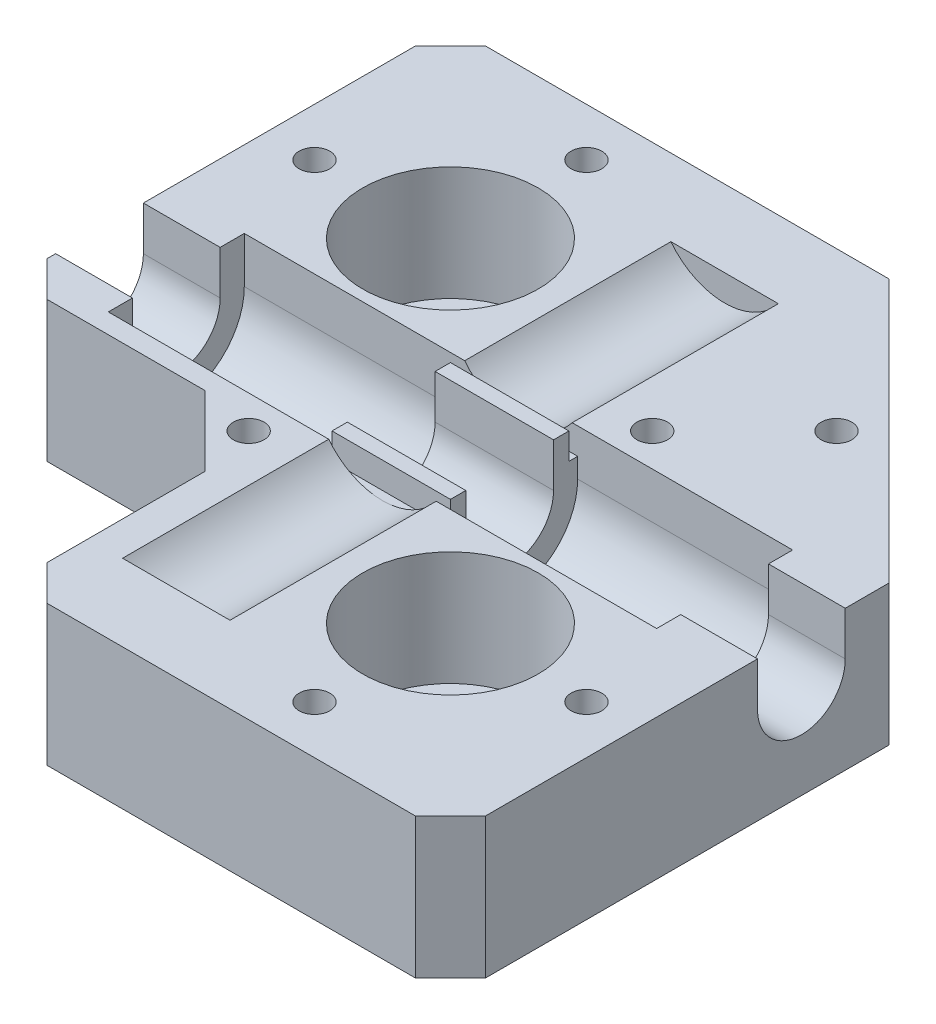
SolidWorks part; units mm, degrees
ref_plane "Front Plane" through (0, 0, 0) normal (0, 0, 1) x (1, 0, 0)
ref_plane "Top Plane" through (0, 0, 0) normal (0, 1, 0) x (1, 0, 0)
ref_plane "Right Plane" through (0, 0, 0) normal (1, 0, 0) x (0, 0, -1)
sketch "Sketch1" plane through (0, 0, 0) normal (0, 1, 0) x (1, 0, 0)
  line L1 (-40, -40) -> (40, -40)
  line L2 (-40, -40) -> (-40, 40)
  line L3 (-40, 40) -> (40, 40)
  line L4 (40, -40) -> (40, 40)
  line L5 (-40, -40) -> (40, 40) construction
  line L6 (-40, 40) -> (40, -40) construction
  point P0 (0, 0)
  dimension "D1" = 80
  dimension "D2" = 80
extrude "Boss-Extrude1" add sketch "Sketch1" against normal blind 16
sketch "Sketch2" plane through (0, 0, 0) normal (0, 1, 0) x (1, 0, 0)
  circle A0 centre (-11.5, -11.5) radius 1.75
  circle A1 centre (11.5, 11.5) radius 1.75
  circle A2 centre (22, 22) radius 1.75
  circle A3 centre (19, -34.5) radius 1.75
  circle A4 centre (34.5, -19) radius 1.75
  circle A5 centre (-34.5, 19) radius 1.75
  circle A6 centre (-19, 34.5) radius 1.75
  dimension "D1" = 3.5
  dimension "D2" = 3.5
  dimension "D3" = 3.5
  dimension "D4" = 3.5
  dimension "D5" = 3.5
  dimension "D6" = 3.5
  dimension "D7" = 3.5
  dimension "D8" = 11.5
  dimension "D9" = 11.5
  dimension "D10" = 11.5
  dimension "D11" = 11.5
  dimension "D12" = 22
  dimension "D13" = 22
  dimension "D14" = 34.5
  dimension "D15" = 34.5
  dimension "D16" = 19
  dimension "D17" = 19
  dimension "D18" = 34.5
  dimension "D19" = 19
  dimension "D20" = 19
  dimension "D21" = 34.5
extrude "Cut-Extrude1" cut sketch "Sketch2" against normal through all both and the other way through all
sketch "Sketch3" plane through (0, 0, 0) normal (0, 1, 0) x (1, 0, 0)
  line L1 (31.25, -7.75) -> (6.75, -7.75)
  line L2 (31.25, -7.75) -> (31.25, 7.75)
  line L3 (31.25, 7.75) -> (6.75, 7.75)
  line L4 (6.75, -7.75) -> (6.75, 7.75)
  line L5 (31.25, -7.75) -> (6.75, 7.75) construction
  line L6 (31.25, 7.75) -> (6.75, -7.75) construction
  line L7 (-6.75, -7.75) -> (-31.25, -7.75)
  line L8 (-6.75, -7.75) -> (-6.75, 7.75)
  line L9 (-6.75, 7.75) -> (-31.25, 7.75)
  line L10 (-31.25, -7.75) -> (-31.25, 7.75)
  line L11 (-6.75, -7.75) -> (-31.25, 7.75) construction
  line L12 (-6.75, 7.75) -> (-31.25, -7.75) construction
  point P0 (19, 0)
  point P5 (-19, 0)
  dimension "D1" = 15.5
  dimension "D2" = 0
  dimension "D3" = 24.5
  dimension "D4" = 19
  dimension "D5" = 24.5
  dimension "D6" = 15.5
  dimension "D7" = 0
  dimension "D8" = 19
extrude "Cut-Extrude2" cut sketch "Sketch3" against normal blind 13
fillet "Fillet1" radius 7.75 4 edges at (19, -13, 7.75) (19, -13, -7.75) (-19, -13, 7.75) (-19, -13, -7.75)
sketch "Sketch4" plane through (0, 0, 0) normal (0, 1, 0) x (1, 0, 0)
  line L1 (-7.75, -31.25) -> (7.75, -31.25)
  line L2 (-7.75, -31.25) -> (-7.75, -6.75)
  line L3 (-7.75, -6.75) -> (7.75, -6.75)
  line L4 (7.75, -31.25) -> (7.75, -6.75)
  line L5 (-7.75, -31.25) -> (7.75, -6.75) construction
  line L6 (-7.75, -6.75) -> (7.75, -31.25) construction
  line L7 (-7.75, 6.75) -> (7.75, 6.75)
  line L8 (-7.75, 6.75) -> (-7.75, 31.25)
  line L9 (-7.75, 31.25) -> (7.75, 31.25)
  line L10 (7.75, 6.75) -> (7.75, 31.25)
  point P0 (0, -19)
  dimension "D1" = 15.5
  dimension "D2" = 0
  dimension "D3" = 24.5
  dimension "D4" = 19
  dimension "D5" = 24.5
  dimension "D6" = 6.75
  dimension "D7" = 15.5
  dimension "D8" = 7.75
extrude "Cut-Extrude3" cut sketch "Sketch4" against normal blind 3
sketch3d "3DSketch1" [suppressed]
  line L1 (-8, -3, 8) -> (8, -3, 8)
  line L2 (-8, -3, 8) -> (-8, 0, 8)
  line L3 (-8, 0, 8) -> (8, 0, 8)
  line L4 (8, -3, 8) -> (8, 0, 8)
  circle A0 centre (0, 5, 8) radius 8
  point P2 (0, 5, 16)
  point P3 (0, 0, 8)
  point P5 (0, 0, 8)
  dimension "D4" = 16
  dimension "D1" = 8
  dimension "D2" = 0
  dimension "D3" = 5
sketch "Sketch5" plane through (0, 0, 31.25) normal (0, 0, -1) x (-1, 0, 0)
  line L0 (7.75, -3) -> (-7.75, -3) construction
  line L5 (7.75, 0) -> (-7.75, 0)
  line L6 (-7.75, 0) -> (-7.75, -3)
  line L7 (-7.75, -3) -> (7.75, -3)
  line L8 (7.75, -3) -> (7.75, 0)
  line L9 (7.75, 0) -> (-7.75, 0)
  line L10 (-7.75, 0) -> (-7.75, -3)
  line L11 (-7.75, -3) -> (7.75, -3)
  line L12 (7.75, -3) -> (7.75, 0)
  circle A0 centre (0, 4.75) radius 7.75
  line M6 (7.75, 0) -> (-7.75, 0)
  line M7 (-7.75, 0) -> (-7.75, -3)
  line M8 (-7.75, -3) -> (7.75, -3)
  line M9 (7.75, -3) -> (7.75, 0)
  dimension "D2" = 15.5
  dimension "D1" = 7.75
  dimension "D3" = 0
extrude "Boss-Extrude2" add sketch "Sketch5" along normal blind 23.5 contours A0 M6 M7 M8 | A0 L11 M9 M6 region at (-5.7238, -1.841, 31.25) region at (5.7238, -1.841, 31.25)
mirror "Mirror1" about plane through (0, 0, 0) normal (0, 0, 1) of "Boss-Extrude2"
sketch "Sketch6" plane through (0, 0, 0) normal (1, 0, 0) x (0, 0, -1)
  line L1 (5, -5) -> (-5, -5)
  line L2 (5, -5) -> (5, 0)
  line L3 (5, 0) -> (-5, 0)
  line L4 (-5, -5) -> (-5, 0)
  circle A0 centre (0, -5) radius 5
  dimension "D2" = 10
  dimension "D1" = 5
extrude "Cut-Extrude4" cut sketch "Sketch6" against normal through all both and the other way through all contours L1 A0 | A0 L3 L4 | A0 L2 L3 | L1 A0 region at (0, -7.1221, 0) region at (0, -1.1168, -3.8832) region at (0, -2.8779, 0) region at (0, -1.1168, 3.8832)
sketch "Sketch7" plane through (0, 0, 0) normal (0, 1, 0) x (1, 0, 0)
  circle A0 centre (19, -19) radius 10
  circle A1 centre (-19, 19) radius 10
  dimension "D5" = 20
  dimension "D6" = 20
  dimension "D1" = 19
  dimension "D2" = 19
  dimension "D3" = 19
  dimension "D4" = 19
extrude "Cut-Extrude5" cut sketch "Sketch7" against normal through all both and the other way through all
sketch "Sketch8" plane through (0, 0, -6.75) normal (0, 0, -1) x (-1, 0, 0)
  line L4 (6.75, 0) -> (-6.75, 0)
  line L5 (-6.75, 0) -> (-6.75, -3)
  line L6 (-6.75, -3) -> (6.75, -3)
  line L7 (6.75, -3) -> (6.75, 0)
  line L8 (6.75, 0) -> (-6.75, 0)
  line L9 (-6.75, 0) -> (-6.75, -3)
  line L10 (-6.75, -3) -> (6.75, -3)
  line L11 (6.75, -3) -> (6.75, 0)
  arc A0 (0, -3) -> (6.1237, 0) centre (0, 4.75) ccw construction
  arc A1 (-6.1237, 0) -> (0, -3) centre (0, 4.75) ccw construction
  arc A2 (0, -3) -> (6.1237, 0) centre (0, 4.75) ccw
  arc A3 (-6.1237, 0) -> (0, -3) centre (0, 4.75) ccw
  line M5 (6.75, 0) -> (-6.75, 0)
  line M6 (-6.75, 0) -> (-6.75, -3)
  line M7 (-6.75, -3) -> (6.75, -3)
  line M8 (6.75, -3) -> (6.75, 0)
  dimension "D1" = 0
extrude "Boss-Extrude3" [suppressed] add sketch "Sketch8" along normal blind 1.5 contours A3 M5 M6 M7 | A2 L10 M8 M5
mirror "Mirror2" [suppressed] about plane through (0, 0, 0) normal (0, 0, 1)
sketch "Sketch9" plane through (0, 0, 0) normal (0, 1, 0) x (1, 0, 0)
  line L0 (-10, -18) -> (-18, -10)
  line L1 (-40, -40) -> (-10, -40)
  line L2 (-40, -40) -> (-40, -10)
  line L3 (-40, -10) -> (-10, -10)
  line L4 (-10, -40) -> (-10, -10)
  line L5 (-10, -10) -> (-18, -10)
  line L6 (-10, -10) -> (-10, -18)
  line L7 (-10, -18) -> (-18, -18)
  line L8 (-18, -10) -> (-18, -18)
  dimension "D1" = 30
  dimension "D2" = 30
  dimension "D3" = 8
  dimension "D4" = 8
extrude "Cut-Extrude6" cut sketch "Sketch9" against normal through all both and the other way through all contours L0 L8 L7 | L8 L3 L2 L1 L4 L7 region at (-15.3333, 0, 15.3333) region at (-25.8421, 0, 25.8421)
chamfer "Chamfer1" distance 4 angle 45 4 edges at (40, -8, 40) (-40, -8, -40) (-40, -8, 10) (-10, -8, 40)
chamfer "Chamfer2" distance 30 angle 45 1 edges at (40, -8, -40)
sketch "Sketch11" plane through (0, -16, 0) normal (0, -1, 0) x (1, 0, 0)
  circle A0 centre (-19, -19) radius 10 construction
  circle A1 centre (19, 19) radius 10 construction
  circle A2 centre (-19, -19) radius 10
  circle A3 centre (19, 19) radius 10
  circle A4 centre (-19, -19) radius 4.25
  circle A5 centre (19, 19) radius 4.25
  dimension "D1" = 8.5
  dimension "D2" = 8.5
extrude "Boss-Extrude4" add sketch "Sketch11" against normal blind 3
sketch "Sketch12" plane through (0, -16, 0) normal (0, -1, 0) x (1, 0, 0)
  circle A0 centre (0, 0) radius 4
  circle A1 centre (16.75, -16.75) radius 4
  dimension "D1" = 8
  dimension "D4" = 8
  dimension "D2" = 16.75
  dimension "D3" = 16.75
extrude "Cut-Extrude7" cut sketch "Sketch12" against normal blind 5
sketch "Sketch13" plane through (0, -16, 0) normal (0, -1, 0) x (1, 0, 0)
  circle A0 centre (22, -22) radius 1.75 construction
  circle A1 centre (11.5, -11.5) radius 1.75 construction
  circle A2 centre (-19, -34.5) radius 1.75 construction
  circle A3 centre (-34.5, -19) radius 1.75 construction
  circle A4 centre (-11.5, 11.5) radius 1.75 construction
  circle A5 centre (34.5, 19) radius 1.75 construction
  circle A6 centre (19, 34.5) radius 1.75 construction
  circle A7 centre (22, -22) radius 1.75
  circle A8 centre (11.5, -11.5) radius 1.75
  circle A9 centre (-19, -34.5) radius 1.75
  circle A10 centre (-34.5, -19) radius 1.75
  circle A11 centre (-11.5, 11.5) radius 1.75
  circle A12 centre (34.5, 19) radius 1.75
  circle A13 centre (19, 34.5) radius 1.75
  circle A14 centre (19, 34.5) radius 3
  circle A15 centre (34.5, 19) radius 3
  circle A16 centre (-11.5, 11.5) radius 3
  circle A17 centre (-34.5, -19) radius 3
  circle A18 centre (-19, -34.5) radius 3
  circle A19 centre (11.5, -11.5) radius 3
  circle A20 centre (22, -22) radius 3
  dimension "D1" = 6
  dimension "D2" = 6
  dimension "D3" = 6
  dimension "D4" = 6
  dimension "D5" = 6
  dimension "D6" = 6
  dimension "D7" = 6
extrude "Cut-Extrude8" cut sketch "Sketch13" against normal blind 10
